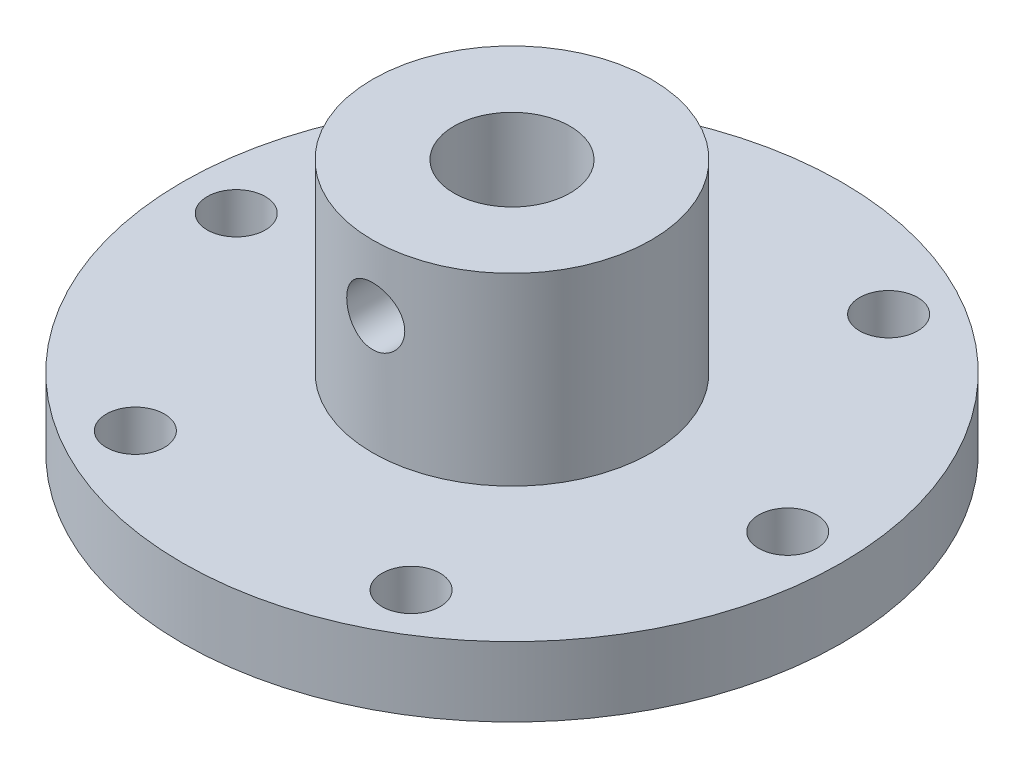
SolidWorks part; units mm, degrees
material "6063-O"
ref_plane "Front Plane" through (0, 0, 0) normal (0, 0, 1) x (1, 0, 0)
ref_plane "Top Plane" through (0, 0, 0) normal (0, 1, 0) x (1, 0, 0)
ref_plane "Right Plane" through (0, 0, 0) normal (1, 0, 0) x (0, 0, -1)
sketch "Sketch1" plane through (0, 0, 0) normal (0, 1, 0) x (1, 0, 0)
  circle A0 centre (0, 0) radius 28.4
  dimension "D1" = 56.8
extrude "Boss-Extrude1" add sketch "Sketch1" along normal blind 6
sketch "Sketch2" plane through (0, 6, 0) normal (0, 1, 0) x (1, 0, 0)
  circle A0 centre (0, 0) radius 12
  dimension "D1" = 24
extrude "Boss-Extrude2" add sketch "Sketch2" along normal blind 15.875
sketch "Sketch3" plane through (0, 21.875, 0) normal (0, 1, 0) x (1, 0, 0)
  circle A0 centre (0, 0) radius 5
  dimension "D1" = 10
extrude "Cut-Extrude1" cut sketch "Sketch3" against normal through all
sketch "Sketch4" plane through (0, 0, 0) normal (0, 0, 1) x (1, 0, 0)
  line L0 (0, 0) -> (0, 21.875) construction
  line L1 (5, 21.875) -> (-5, 21.875) construction
  circle A0 centre (0, 16.2) radius 3
  dimension "D1" = 6
  dimension "D3" = 16.2
hole_wizard "M6x1.0 Tapped Hole1" positions "Sketch5" profile "Sketch7" tap size "M6x1.0" standard "ANSI Metric" end condition through all
sketch "Sketch5" plane through (0, 0, 0) normal (0, 0, 1) x (1, 0, 0)
  point P0 (0, 16.2)
  point P7 (0, 0)
sketch "Sketch7" plane through (0, 16.2, 0) normal (1, 0, 0) x (0, 1, 0)
  line L0 (0, 0) -> (0, 28.4)
  line L1 (0, 28.4) -> (2.5, 28.4)
  line L2 (2.5, 28.4) -> (2.5, 0)
  line L5 (2.5, 0) -> (0, 0)
  line L11 (0, -6.35) -> (0, 107.95) construction
  dimension "Thru Tap Drill Dia." = 5
  dimension "Thru Tap Drill Depth" = 28.4
cosmetic thread "Hole Thread2" parameters "D2"=6
sketch "Sketch8" plane through (0, 0, 0) normal (0, -1, 0) x (1, 0, 0)
  circle A0 centre (0, 0) radius 23.75 construction
  circle A1 centre (-23.75, 0) radius 2.6
  circle A2 centre (-11.875, 20.5681) radius 2.6
  circle A3 centre (11.875, 20.5681) radius 2.6
  circle A4 centre (23.75, 0) radius 2.6
  circle A5 centre (11.875, -20.5681) radius 2.6
  circle A6 centre (-11.875, -20.5681) radius 2.6
  point P6 (-11.8755, -20.5678)
  point P7 (-8.4502, -22.1959)
  point P17 (0, 0)
  point P18 (12.1221, -20.4235)
  dimension "D1" = 47.5
  dimension "D2" = 5.2
  dimension "D3" = 6
hole_wizard "M6 Tapped Hole1" positions "Sketch9" profile "Sketch10" tap size "M6" standard "AS" end condition through all
sketch "Sketch9" plane through (0, 0, 0) normal (0, -1, 0) x (-1, 0, 0)
  point P0 (23.75, 0)
  point P3 (11.875, -20.5681)
  point P6 (-11.875, -20.5681)
  point P9 (-23.75, 0)
  point P12 (-11.875, 20.5681)
  point P15 (11.875, 20.5681)
sketch "Sketch10" plane through (-23.75, 0, 0) normal (1, 0, 0) x (0, 0, -1)
  line L0 (0, 0) -> (0, 21.875)
  line L1 (0, 21.875) -> (2.5, 21.875)
  line L2 (2.5, 21.875) -> (2.5, 0)
  line L5 (2.5, 0) -> (0, 0)
  line L11 (0, -6.35) -> (0, 107.95) construction
  dimension "Thru Tap Drill Dia." = 5
  dimension "Thru Tap Drill Depth" = 21.875
cosmetic thread "Hole Thread3" parameters "D2"=6
cosmetic thread "Hole Thread4" parameters "D2"=6
cosmetic thread "Hole Thread5" parameters "D2"=6
cosmetic thread "Hole Thread6" parameters "D2"=6
cosmetic thread "Hole Thread7" parameters "D2"=6
cosmetic thread "Hole Thread8" parameters "D2"=6
